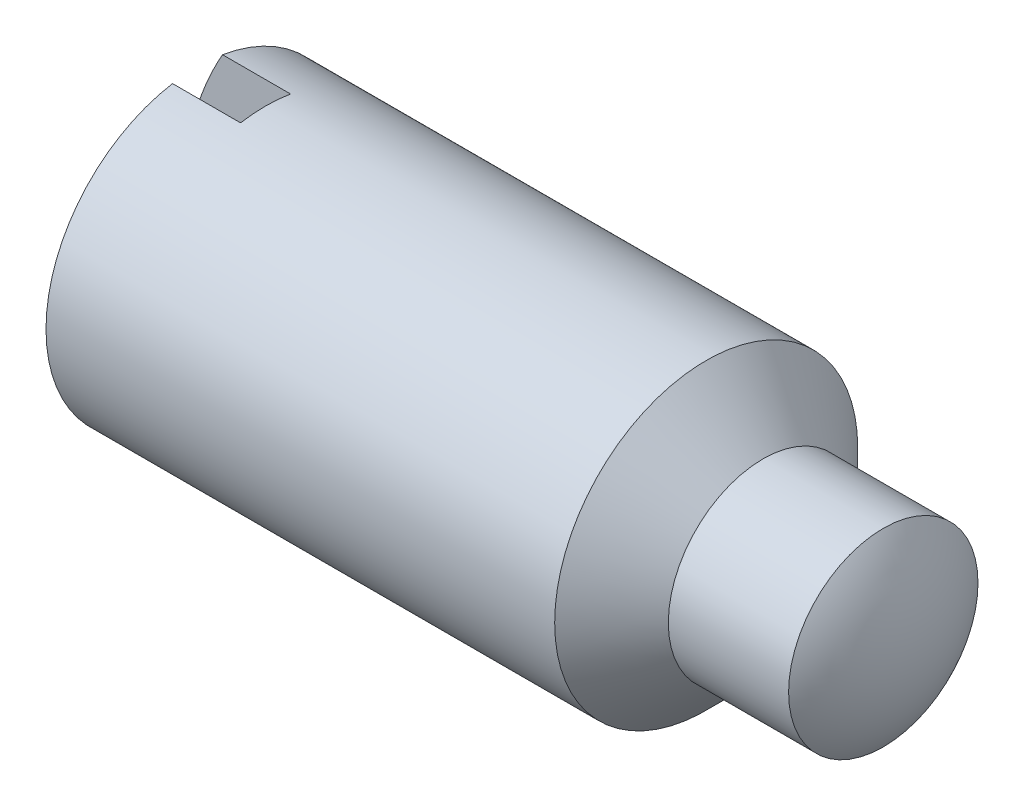
SolidWorks part; units mm, degrees
ref_plane "Front" through (0, 0, 0) normal (0, 0, 1) x (1, 0, 0)
ref_plane "Top" through (0, 0, 0) normal (0, 1, 0) x (1, 0, 0)
ref_plane "Right" through (0, 0, 0) normal (1, 0, 0) x (0, 0, -1)
sketch "Sketch1" plane through (11.1469, 0, 2) normal (0, 1, 0) x (1, 0, 0)
  line L0 (-1.1469, 2) -> (-11.1469, 2)
  line L2 (-1.5594, 3.25) -> (-3.1469, 3.25)
  line L3 (-3.1469, 3.25) -> (-3.8969, 4)
  line L4 (-3.8969, 4) -> (-10.611, 4)
  line L5 (-15.3263, 2) -> (1.8856, 2) construction
  arc A0 (-10.611, 4) -> (-11.1469, 2) centre (-7.1469, 2) ccw
  arc A1 (-1.1469, 2) -> (-1.5594, 3.25) centre (-3.2469, 2) ccw
  dimension "D1" = 45
  dimension "l" = 8
revolve "Base" add sketch "Sketch1" angle 360 about L5
cosmetic thread "ThreadCosmetic1" [suppressed] parameters "D2"=3
sketch "Sketch2" plane through (0, 0, 0) normal (0, 1, 0) x (1, 0, 0)
  line L0 (-0.4638, 0) -> (0.2879, 0) construction
  line L1 (1.4336, 0.33) -> (0.0136, 0.33)
  line L2 (1.4336, 0.33) -> (1.4336, -0.33)
  line L3 (1.4336, -0.33) -> (0.0136, -0.33)
  arc A2 (0.5359, 2) -> (0.5359, -2) centre (4, 0) ccw construction
  arc A3 (0.0136, 0.33) -> (0.0136, -0.33) centre (0.0136, 0) ccw
  dimension "m" = 0.33
extrude "Slot" cut sketch "Sketch2" against normal through all and the other way through all
sketch "Sketch3" plane through (0, 0, 0) normal (0, 1, 0) x (1, 0, 0)
  line L0 (7.25, 1.567) -> (7.5, 2)
  line L1 (7.5, 2) -> (7.5, 2.5)
  line L2 (7.5, 2.5) -> (7, 2.5)
  line L3 (7, 2.5) -> (7, 2)
  line L4 (7, 2) -> (7.25, 1.567)
  line L5 (7.25, -2) -> (7.25, 2) construction
  line L6 (7.25, 2) -> (0.5359, 2) construction
  line L7 (0, 0) -> (11.0187, 0) construction
revolve "Cut-Revolve10" [suppressed] cut sketch "Sketch3" angle 360 about L7
pattern_linear "LPattern10" [suppressed] count 12 spacing 0.6 along (-1, 0, 0) of bodies 103
equation "\"re@Sketch1\" = \"dp@Sketch1\" - \"z@Sketch1\" / 5"
equation "\"m@Sketch2\" = \"n@Sketch2\" / 2"
equation "\"D1@Sketch3\" =  ( \"d@Sketch1\" - \"D2@ThreadCosmetic1\" )  / 2"
equation "\"D3@LPattern10\" = \"D1@Sketch3\" * 1.2"
equation "\"D1@LPattern10\" = ( \"l@Sketch1\" -  ( \"d@Sketch1\" - \"dp@Sketch1\" )  / 2 )  / \"D3@LPattern10\""
